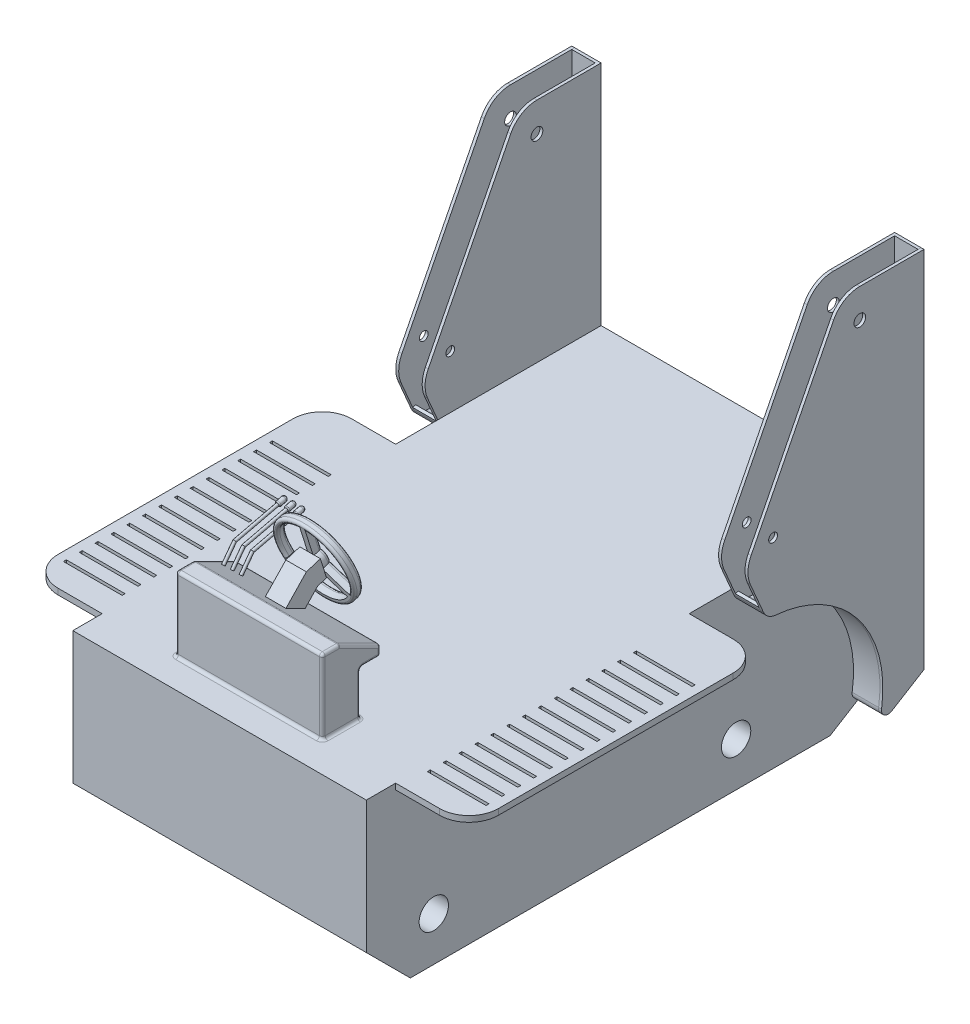
SolidWorks part; units mm, degrees
ref_plane "Front Plane" through (0, 0, 0) normal (0, 0, 1) x (1, 0, 0)
ref_plane "Top Plane" through (0, 0, 0) normal (0, 1, 0) x (1, 0, 0)
ref_plane "Right Plane" through (0, 0, 0) normal (1, 0, 0) x (0, 0, -1)
sketch "Sketch1" plane through (0, 0, 0) normal (1, 0, 0) x (0, 0, -1)
  line L0 (935, 135) -> (935, 600)
  line L1 (935, 600) -> (-865, 600)
  line L2 (-865, 600) -> (-865, 150)
  line L3 (-865, 150) -> (-715, 0)
  line L4 (-715, 0) -> (715, 0)
  line L5 (715, 0) -> (935, 135)
  circle A0 centre (-635, 150) radius 50
  circle A1 centre (395, 150) radius 50
  dimension "D9" = 100
  dimension "D1" = 1800
  dimension "D2" = 600
  dimension "D3" = 150
  dimension "D4" = 150
  dimension "D5" = 220
  dimension "D6" = 135
  dimension "D7" = 1030
  dimension "D8" = 150
  dimension "D10" = 540
extrude "Boss-Extrude1" add sketch "Sketch1" along normal mid plane 1000
sketch "Sketch2" plane through (500, 0, 0) normal (1, 0, 0) x (0, 0, -1)
  line L0 (935, 135) -> (935, 1375)
  line L1 (935, 1375) -> (716.3817, 1375)
  line L2 (627.2141, 1320.2675) -> (346.1637, 766.6563)
  line L3 (343.4168, 681.9969) -> (387.7129, 578.6394)
  line L4 (935, 135) -> (825, 67.5)
  line L5 (715, 0) -> (935, 135) construction
  arc A6 (825, 67.5) -> (790.5254, 90.337) centre (813.0735, 86.9357) cw
  arc A7 (790.5254, 90.337) -> (429.3735, 548.5203) centre (395, 150) ccw
  circle A8 centre (395, 150) radius 50 construction
  arc A9 (346.1637, 766.6563) -> (343.4168, 681.9969) centre (435.3313, 721.3889) ccw
  arc A10 (716.3817, 1375) -> (627.2141, 1320.2675) centre (716.3817, 1275) ccw
  arc A11 (387.7129, 578.6394) -> (429.3735, 548.5203) centre (433.6701, 598.3354) ccw
  point P17 (325.0003, 724.9687)
  point P20 (655, 1375)
  point P23 (400.0003, 549.9687)
  dimension "D5" = 400
  dimension "D6" = 100
  dimension "D7" = 50
  dimension "D1" = 1240
  dimension "D2" = 280
  dimension "D3" = 75
  dimension "D4" = 175
extrude "Boss-Extrude2" add sketch "Sketch2" along normal blind 10
sketch "Sketch10" plane through (510, 0, 0) normal (1, 0, 0) x (0, 0, -1)
  line L0 (387.7129, 578.6394) -> (383.1356, 589.3197)
  line L1 (378.5584, 600) -> (387.7129, 578.6394) construction
  line L2 (825, 67.5) -> (935, 135) construction
  line L3 (935, 135) -> (935, 1375) construction
  line L4 (825, 67.5) -> (935, 135)
  line L5 (935, 135) -> (935, 1375)
  line L6 (396.9043, 582.5786) -> (392.3271, 593.2589)
  line L7 (819.7698, 76.0232) -> (925, 140.5963)
  line L8 (925, 140.5963) -> (925, 1375)
  line L9 (383.1356, 589.3197) -> (392.3271, 593.2589)
  line L10 (925, 1375) -> (935, 1375)
  arc A0 (387.7129, 578.6394) -> (429.3735, 548.5203) centre (433.6701, 598.3354) ccw construction
  arc A1 (790.5254, 90.337) -> (429.3735, 548.5203) centre (395, 150) ccw construction
  arc A2 (790.5254, 90.337) -> (825, 67.5) centre (813.0735, 86.9357) ccw construction
  arc A3 (387.7129, 578.6394) -> (429.3735, 548.5203) centre (433.6701, 598.3354) ccw
  arc A4 (790.5254, 90.337) -> (429.3735, 548.5203) centre (395, 150) ccw
  arc A5 (790.5254, 90.337) -> (825, 67.5) centre (813.0735, 86.9357) ccw
  arc A6 (396.9043, 582.5786) -> (430.2328, 558.4834) centre (433.6701, 598.3354) ccw
  arc A7 (800.4135, 88.8454) -> (430.2328, 558.4834) centre (395, 150) ccw
  arc A8 (800.4135, 88.8454) -> (819.7698, 76.0232) centre (813.0735, 86.9357) ccw
  dimension "D1" = 10
extrude "Boss-Extrude3" add sketch "Sketch10" along normal blind 80
extrude "Boss-Extrude4" add sketch "Sketch2<2>" along normal blind 10 from offset 90 separate body
sketch "Sketch2<2>" plane through (500, 0, 0) normal (1, 0, 0) x (0, 0, -1) same geometry as "Sketch2"
mirror "Mirror3" about plane through (0, 0, 0) normal (1, 0, 0) of bodies 103 104
sketch "Sketch11" plane through (600, 0, 0) normal (1, 0, 0) x (0, 0, -1)
  line L0 (627.2141, 1320.2675) -> (346.1637, 766.6563) construction
  circle A0 centre (716.3817, 1275) radius 20
  circle A1 centre (420.932, 781.3889) radius 15
  arc A2 (346.1637, 766.6563) -> (343.4168, 681.9969) centre (435.3313, 721.3889) ccw construction
  dimension "D1" = 60
  dimension "D3" = 30
  dimension "D4" = 40
  dimension "D2" = 60
extrude "Cut-Extrude1" cut sketch "Sketch11" against normal through all
sketch "Sketch12" plane through (0, 600, 0) normal (0, 1, 0) x (1, 0, 0)
  line L0 (0, 0) -> (0, -710.4307) construction
  line L1 (500, 378.5584) -> (500, -865) construction
  line L2 (500, 235) -> (650, 235)
  line L3 (500, 235) -> (500, -765)
  line L4 (500, -765) -> (650, -765)
  line L5 (750, 135) -> (750, -665)
  line L6 (-750, 135) -> (-750, -665)
  line L7 (-500, -765) -> (-650, -765)
  line L8 (-500, 235) -> (-500, -765)
  line L9 (-500, 235) -> (-650, 235)
  arc A0 (650, -765) -> (750, -665) centre (650, -665) ccw
  arc A1 (650, 235) -> (750, 135) centre (650, 135) cw
  arc A2 (-650, 235) -> (-750, 135) centre (-650, 135) ccw
  arc A3 (-650, -765) -> (-750, -665) centre (-650, -665) cw
  point P12 (750, -765)
  point P15 (750, 235)
  point P24 (-750, 235)
  point P25 (-750, -765)
  dimension "D4" = 100
  dimension "D1" = 1000
  dimension "D2" = 250
  dimension "D3" = 100
extrude "Boss-Extrude5" add sketch "Sketch12" against normal blind 20
sketch "Sketch13" plane through (0, 600, 0) normal (0, 1, 0) x (1, 0, 0)
  line L0 (750, -665) -> (750, 135) construction
  line L1 (520, 35) -> (720, 35)
  line L2 (520, 35) -> (520, 25)
  line L3 (520, 25) -> (720, 25)
  line L4 (720, 35) -> (720, 25)
  line L5 (650, 235) -> (500, 235) construction
  line L6 (0, 0) -> (0, -255.7722) construction
  line L7 (-720, 35) -> (-720, 25)
  line L8 (-520, 25) -> (-720, 25)
  line L9 (-520, 35) -> (-520, 25)
  line L10 (-520, 35) -> (-720, 35)
  dimension "D1" = 200
  dimension "D2" = 30
  dimension "D3" = 10
  dimension "D4" = 200
extrude "Cut-Extrude2" cut sketch "Sketch13" against normal through all
pattern_linear "LPattern1" count 14 spacing 54 along (0, 0, 1) of "Cut-Extrude2"
sketch "Sketch14" plane through (0, 600, 0) normal (0, 1, 0) x (1, 0, 0)
  line L0 (500, -865) -> (-500, -865) construction
  line L1 (250, -565) -> (-250, -565)
  line L2 (250, -565) -> (250, -765)
  line L3 (250, -765) -> (-250, -765)
  line L4 (-250, -565) -> (-250, -765)
  line L5 (250, -565) -> (-250, -765) construction
  line L6 (250, -765) -> (-250, -565) construction
  point P0 (0, -665)
  dimension "D1" = 500
  dimension "D2" = 200
  dimension "D3" = 100
extrude "Boss-Extrude6" add sketch "Sketch14" along normal blind 253
sketch "Sketch15" plane through (250, 0, 0) normal (1, 0, 0) x (0, 0, -1)
  line L0 (-565, 783) -> (-705, 853)
  line L1 (-565, 853) -> (-565, 600) construction
  line L3 (-705, 853) -> (-565, 853)
  line L4 (-565, 853) -> (-565, 783)
  line L6 (-565, 600) -> (-635, 600)
  line L7 (-565, 600) -> (-565, 750)
  line L8 (-565, 750) -> (-635, 750)
  line L9 (-635, 600) -> (-635, 750)
  dimension "D1" = 70
  dimension "D2" = 150
  dimension "D3" = 140
  dimension "D4" = 70
extrude "Cut-Extrude3" cut sketch "Sketch15" against normal through all
fillet "Fillet1" radius 10 21 edges at (0, 750, 565) (0, 600, 635) (0, 750, 635) (-250, 600, 700) (-250, 675, 635) (-250, 750, 600) (-250, 766.5, 565) (-250, 853, 735) (-250, 726.5, 765) (0, 853, 765) (0, 600, 765) (-250, 818, 635) (0, 783, 565) (0, 853, 705) (250, 750, 600) (250, 675, 635) (250, 600, 700) (250, 726.5, 765) (250, 853, 735) (250, 818, 635) (250, 766.5, 565)
ref_plane "Plane2" through (-220, 0, 0) normal (-1, 0, 0) x (0, 0, 1)
sketch "Sketch18" plane through (-220, 0, 0) normal (-1, 0, 0) x (0, 0, 1)
  line L0 (631.6595, 817.1287) -> (593.3857, 868.73)
  line L1 (570.5279, 785.7639) -> (702.8885, 851.9443) construction
  line L2 (593.3857, 868.73) -> (447.4906, 903.5812)
  dimension "D1" = 140
  dimension "D2" = 100
  dimension "D3" = 150
  dimension "D4" = 116.8432
  dimension "D5" = 80
ref_plane "Plane3" through (-220, 903.5812, 447.4906) normal (0, 0.2323, -0.9726) x (-1, 0, 0)
sketch "Sketch19" plane through (-220, 903.5812, 447.4906) normal (0, 0.2323, -0.9726) x (-1, 0, 0)
  circle A0 centre (-0.2948, 0.4499) radius 5
  dimension "D1" = 10
sweep "Sweep1" add profiles "Sketch19" path "Sketch18"
sketch "Sketch20" plane through (0, -52.3478, 219.1399) normal (0, 0.2323, -0.9726) x (-1, 0, 0)
  circle A0 centre (219.7052, 983.2745) radius 8.5
  dimension "D1" = 17
extrude "Boss-Extrude7" add sketch "Sketch20" along normal blind 30 separate body
fillet "Fillet2" radius 8.5 1 edges at (-219.7052, 919.2564, 420.391)
fillet "Fillet3" radius 3.5 1 edges at (-219.7052, 912.2862, 449.57)
sketch "Sketch21" plane through (0, 0, 0) normal (1, 0, 0) x (0, 0, -1)
  line L0 (-673.8231, 837.4116) -> (-604.1436, 910.5263)
  line L1 (-702.8885, 851.9443) -> (-570.5279, 785.7639) construction
  line L2 (-604.1436, 910.5263) -> (-556.4259, 925.4601)
  line L3 (-556.4259, 925.4601) -> (-535.5185, 858.6553)
  line L4 (-535.5185, 858.6553) -> (-565.9594, 849.1285)
  line L5 (-565.9594, 849.1285) -> (-608.3325, 804.6663)
  line L6 (-673.8231, 837.4116) -> (-608.3325, 804.6663)
  dimension "D1" = 101
  dimension "D2" = 151
  dimension "D3" = 50
  dimension "D4" = 70
  dimension "D5" = 34
  dimension "D6" = 70
extrude "Boss-Extrude8" add sketch "Sketch21" along normal mid plane 70
sketch "Sketch22" plane through (0, -76.0473, 242.9925) normal (0, 0.2987, -0.9544) x (-1, 0, 0)
  line L0 (-35, 1049.4082) -> (35, 1049.4082) construction
  line L1 (-35, 979.4082) -> (-35, 1049.4082) construction
  circle A0 centre (0, 1014.4082) radius 12.5
  dimension "D1" = 25
  dimension "D2" = 35
  dimension "D3" = 35
extrude "Boss-Extrude9" add sketch "Sketch22" along normal mid plane 30
sketch "Sketch23" plane through (0, -71.5672, 228.6772) normal (0, 0.2987, -0.9544) x (-1, 0, 0)
  line L1 (0, 1014.4082) -> (0, 1131.4082) construction
  line L2 (-9, 1131.0616) -> (-9, 1043.0264)
  line L3 (9, 1131.0616) -> (9, 1043.0264)
  line L4 (105.5247, 963.8758) -> (29.2841, 1007.8934)
  line L5 (96.5247, 948.2873) -> (20.2841, 992.3049)
  line L6 (-96.5247, 948.2873) -> (-20.2841, 992.3049)
  line L7 (-105.5247, 963.8758) -> (-29.2841, 1007.8934)
  arc A0 (-96.5247, 948.2873) -> (96.5247, 948.2873) centre (0, 1014.4082) ccw
  circle A1 centre (0, 1014.4082) radius 135
  arc A2 (-9, 1043.0264) -> (-29.2841, 1007.8934) centre (0, 1014.4082) ccw
  arc A3 (-20.2841, 992.3049) -> (20.2841, 992.3049) centre (0, 1014.4082) ccw
  arc A4 (29.2841, 1007.8934) -> (9, 1043.0264) centre (0, 1014.4082) ccw
  arc A5 (-9, 1131.0616) -> (-105.5247, 963.8758) centre (0, 1014.4082) ccw
  arc A6 (105.5247, 963.8758) -> (9, 1131.0616) centre (0, 1014.4082) ccw
  point P22 (0, 1014.4082)
  dimension "D1" = 60
  dimension "D2" = 270
  dimension "D3" = 18
  dimension "D4" = 18
  dimension "D5" = 3
extrude "Boss-Extrude10" add sketch "Sketch23" along normal mid plane 30
fillet "Fillet4" radius 9 16 edges at (0, 872.3874, 508.3813) (58.4044, 858.9194, 504.1663) (0, 789.3585, 482.3964) (-58.4044, 858.9194, 504.1663) (-25.9808, 915.3333, 521.8217) (-67.4044, 873.7963, 508.8222) (-101.325, 956.8477, 534.8141) (-9, 970.3383, 539.0361) (25.9808, 915.3333, 521.8217) (9, 970.3383, 539.0361) (101.325, 956.8477, 534.8141) (67.4044, 873.7963, 508.8222) (0, 1029.8559, 557.6629) (101.325, 947.8874, 563.4448) (-101.325, 947.8874, 563.4448) (0, 1020.8956, 586.2935)
pattern_linear "LPattern2" count 3 spacing 30 along (1, 0, 0) of bodies 122 121
